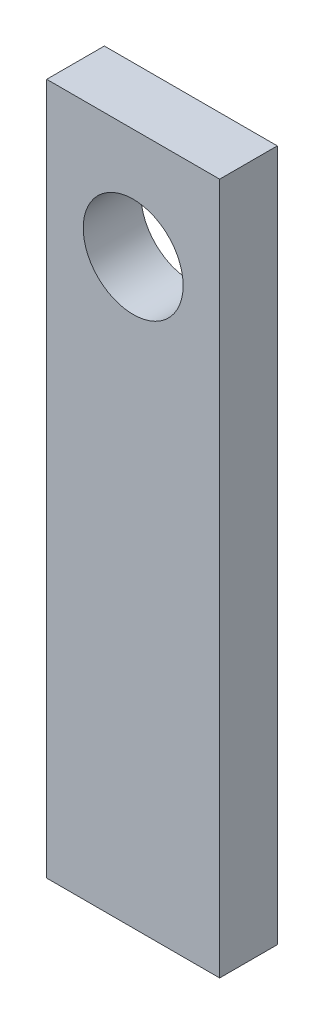
SolidWorks part; units mm, degrees
ref_plane "Plan de face" through (0, 0, 0) normal (0, 0, 1) x (1, 0, 0)
ref_plane "Plan de dessus" through (0, 0, 0) normal (0, 1, 0) x (1, 0, 0)
ref_plane "Plan de droite" through (0, 0, 0) normal (1, 0, 0) x (0, 0, -1)
sketch "Esquisse1" plane through (0, 0, 0) normal (0, 0, 1) x (1, 0, 0)
  line L1 (0, 0) -> (-9, 0)
  line L2 (0, 0) -> (0, 36)
  line L3 (0, 36) -> (-9, 36)
  line L4 (-9, 0) -> (-9, 36)
  circle A0 centre (-4.5, 30.25) radius 2.6
  dimension "D4" = 5.2
  dimension "D5" = 4.5
  dimension "D1" = 36
  dimension "D2" = 9
  dimension "D3" = 30.25
extrude "Boss.-Extru.1" add sketch "Esquisse1" along normal blind 3
